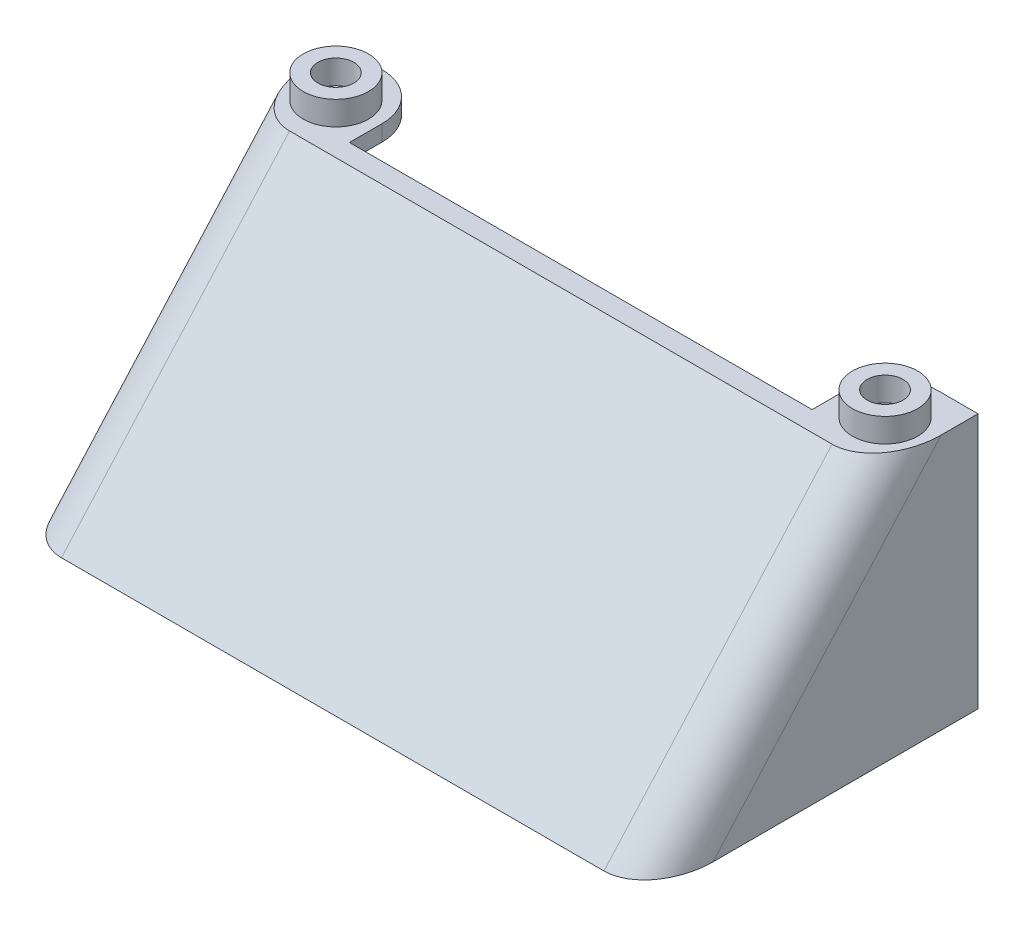
SolidWorks part; units mm, degrees
ref_plane "Front Plane" through (0, 0, 0) normal (0, 0, 1) x (1, 0, 0)
ref_plane "Top Plane" through (0, 0, 0) normal (0, 1, 0) x (1, 0, 0)
ref_plane "Right Plane" through (0, 0, 0) normal (1, 0, 0) x (0, 0, -1)
sketch "Sketch1" plane through (0, 0, 0) normal (1, 0, 0) x (0, 0, -1)
  line L0 (0, 0) -> (0, 19.2)
  line L1 (0, 19.2) -> (-7.46, 19.2)
  line L2 (-7.46, 19.2) -> (-24.5905, 0)
  line L3 (-24.5905, 0) -> (0, 0)
  dimension "D1" = 19.2
  dimension "D2" = 24.5905
  dimension "D3" = 7.46
extrude "Boss-Extrude1" add sketch "Sketch1" against normal blind 47.75
shell "Shell2" thickness 1.2 removed face at (-23.875, 0, 12.2952)
sketch "Sketch2" plane through (0, 0, 1.2) normal (0, 0, 1) x (1, 0, 0)
  line L0 (-46.55, 0) -> (-46.55, 17.927)
  line L1 (-46.55, 0) -> (-1.2, 0) construction
  line L2 (-46.55, 17.927) -> (-1.2, 17.927)
  line L3 (-1.2, 17.927) -> (-1.2, 0)
  line L4 (-1.2, 0) -> (-46.55, 0)
  point P4 (-46.55, 8.9635)
  point P7 (-1.2, 8.9635)
  dimension "D1" = 17.927
  dimension "D2" = 45.35
extrude "Cut-Extrude1" cut sketch "Sketch2" against normal through all
sketch "Sketch3" plane through (0, 19.2, 0) normal (0, 1, 0) x (1, 0, 0)
  line L0 (-41.25, 0) -> (-41.25, -5.96)
  line L1 (-47.75, 0) -> (0, 0) construction
  line L2 (-41.25, -5.96) -> (-6.5, -5.96)
  line L3 (-6.5, -5.96) -> (-6.5, 0)
  line L4 (-47.75, -7.46) -> (0, -7.46) construction
  line L5 (0, 0) -> (0, -7.46) construction
  line L6 (-47.75, 0) -> (-47.75, -7.46) construction
  dimension "D1" = 1.5
  dimension "D2" = 6.5
  dimension "D3" = 6.5
extrude "Cut-Extrude2" cut sketch "Sketch3" against normal through all and the other way through all
sketch "Sketch5" plane through (0, 0, 0) normal (0, -1, 0) x (1, 0, 0)
  line L0 (-47.75, 0) -> (-39.95, 0)
  line L1 (-41.25, 0) -> (-46.55, 0) construction
  line L2 (-39.95, 0) -> (-39.95, 16.7905)
  line L3 (-39.95, 16.7905) -> (-7.8, 16.7905)
  line L4 (-7.8, 16.7905) -> (-7.8, 0)
  line L5 (-1.2, 0) -> (-6.5, 0) construction
  line L6 (-7.8, 0) -> (0, 0)
  line L7 (0, 0) -> (0, 24.5905)
  line L8 (0, 24.5905) -> (-47.75, 24.5905)
  line L9 (-47.75, 24.5905) -> (0, 24.5905) construction
  line L10 (-47.75, 24.5905) -> (-47.75, 0) construction
  line L11 (-47.75, 24.5905) -> (-47.75, 0)
  dimension "D1" = 7.8
  dimension "D2" = 7.8
  dimension "D3" = 7.8
extrude "Boss-Extrude2" add sketch "Sketch5" against normal blind 3.5
sketch "Sketch6" plane through (-47.75, 0, 0) normal (-1, 0, 0) x (0, 0, 1)
  line L0 (21.4677, 3.5) -> (24.5905, 0)
  line L1 (24.5905, 0) -> (24.5905, 3.5)
  line L2 (24.5905, 3.5) -> (21.4677, 3.5)
extrude "Cut-Extrude3" cut sketch "Sketch6" against normal through all
sketch "Sketch7" plane through (0, 19.2, 0) normal (0, 1, 0) x (1, 0, 0)
  line L1 (-47.75, 0) -> (-47.75, -7.46) construction
  line L2 (-47.75, 0) -> (-41.25, 0) construction
  line L3 (0, 0) -> (0, -7.46) construction
  line L4 (-6.5, 0) -> (0, 0) construction
  circle A0 centre (-44.5, -3.73) radius 2.45
  circle A1 centre (-44.5, -3.73) radius 1.35
  circle A2 centre (-3.25, -3.73) radius 2.45
  circle A3 centre (-3.25, -3.73) radius 1.35
  dimension "D1" = 3.25
  dimension "D3" = 3.25
  dimension "D5" = 4.9
  dimension "D6" = 2.7
  dimension "D7" = 4.9
  dimension "D8" = 2.7
  dimension "D2" = 3.73
  dimension "D4" = 3.73
extrude "Boss-Extrude3" add sketch "Sketch7" along normal blind 1.8
shell "Shell3" thickness 1.5 removed face at (-23.875, 0, 10.3452)
sketch "Sketch8" plane through (0, 2, 0) normal (0, -1, 0) x (1, 0, 0)
  line L1 (-47.75, 24.5905) -> (-47.75, 0) construction
  line L2 (-47.75, 0) -> (-39.95, 0) construction
  line L3 (-23.875, 30.6147) -> (-23.875, -1.9188) construction
  line L5 (0, 24.5905) -> (0, 0) construction
  circle A0 centre (-43.85, 8.1967) radius 1.5
  circle A1 centre (-43.85, 8.1967) radius 0.7
  circle A2 centre (-43.85, 16.3933) radius 0.7
  circle A3 centre (-43.85, 16.3933) radius 1.5
  circle A4 centre (-3.9, 16.3933) radius 1.5
  circle A5 centre (-3.9, 16.3933) radius 0.7
  circle A6 centre (-3.9, 8.1967) radius 0.7
  circle A7 centre (-3.9, 8.1967) radius 1.5
  dimension "D4" = 3
  dimension "D5" = 1.4
  dimension "D6" = 8.1967
  dimension "D1" = 3.9
  dimension "D2" = 2
  dimension "D3" = 8.1967
  dimension "D7" = 23.875
extrude "Boss-Extrude4" add sketch "Sketch8" along normal offset from surface (1.8 mm away) 0.2 up to face at (-23.875, 0, 10.9677)
fillet "Fillet1" radius 3.5 4 edges at (-47.75, 9.6, 16.0252) (0, 9.6, 16.0252) (-41.25, 18.5635, 0) (-6.5, 18.5635, 0)
